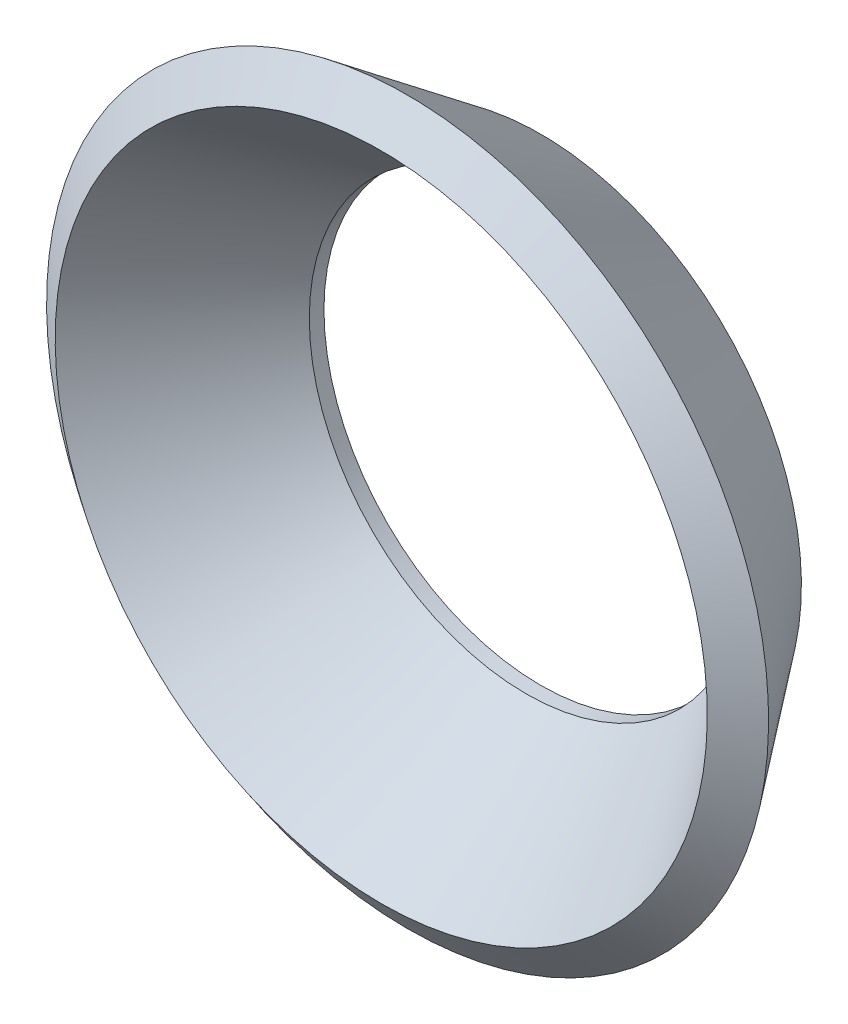
SolidWorks part; units mm, degrees
ref_plane "Front Plane" through (0, 0, 0) normal (0, 0, 1) x (1, 0, 0)
ref_plane "Top Plane" through (0, 0, 0) normal (0, 1, 0) x (1, 0, 0)
ref_plane "Right Plane" through (0, 0, 0) normal (1, 0, 0) x (0, 0, -1)
sketch "Sketch2" plane through (0, 0, 0) normal (1, 0, 0) x (0, 0, -1)
  line L0 (0, 5.2832) -> (0, 0) construction
  line L7 (0, 0) -> (17.2695, 0) construction
  line L14 (0, 5.2832) -> (-3.1735, 5.2832) construction
  line L27 (0, 6.35) -> (-3.2457, 8.7958)
  line L31 (0, 5.2832) -> (0, 6.35)
  line L32 (-0.642, 5.498) -> (-3.8877, 7.9438)
  line L33 (-0.642, 5.498) -> (-0.3569, 5.2832)
  line L34 (-0.3569, 5.2832) -> (0, 5.2832)
  line L35 (-3.2457, 8.7958) -> (-3.8877, 7.9438)
  dimension "D1" = 1.0668
  dimension "D6" = 37
  dimension "D2" = 1.0668
  dimension "D3" = 6.35
  dimension "D4" = 4.064
revolve "Revolve1" add sketch "Sketch2" angle 360 about L7
